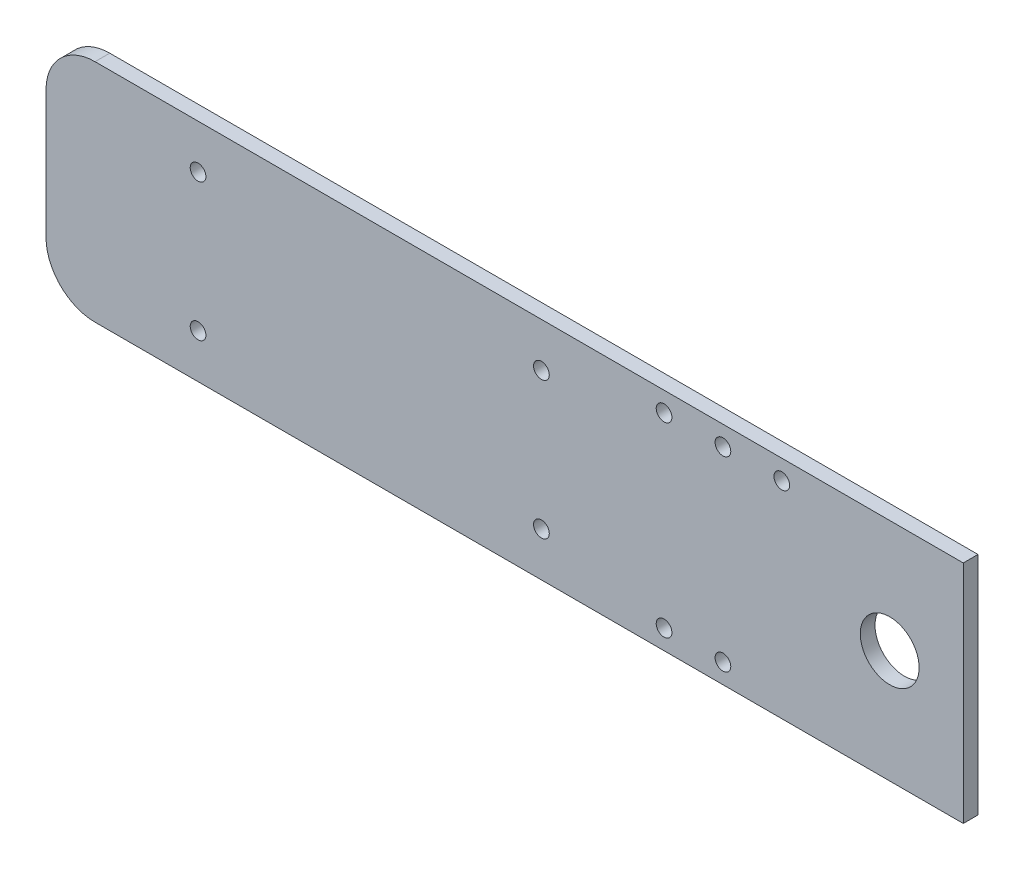
SolidWorks part; units mm, degrees
material "Acrylic (Medium-high impact)"
ref_plane "Front Plane" through (0, 0, 0) normal (0, 0, 1) x (1, 0, 0)
ref_plane "Top Plane" through (0, 0, 0) normal (0, 1, 0) x (1, 0, 0)
ref_plane "Right Plane" through (0, 0, 0) normal (1, 0, 0) x (0, 0, -1)
sketch "Sketch2" plane through (0, 0, 0) normal (0, 0, 1) x (1, 0, 0)
  line L0 (56, 23) -> (56, 17)
  line L1 (56, -23) -> (-56, -23)
  line L2 (56, -23) -> (56, 23)
  line L3 (56, 23) -> (-56, 23)
  line L4 (-56, -23) -> (-56, 23)
  line L5 (56, -23) -> (-56, 23) construction
  line L6 (56, 23) -> (-56, -23) construction
  line L7 (56, 23) -> (86, 23)
  line L8 (56, 23) -> (56, -23)
  line L9 (56, -23) -> (86, -23)
  line L10 (86, 23) -> (86, -23)
  line L11 (0, 0) -> (10, 0)
  line L12 (56, -23) -> (56, -17)
  line L13 (10, 0) -> (10, -14)
  line L14 (10, -14) -> (45, -14)
  circle A0 centre (45, -14) radius 1.6
  circle A1 centre (-25, -14) radius 1.6
  circle A2 centre (45, 14) radius 1.6
  circle A3 centre (-25, 14) radius 1.6
  point P0 (0, 0)
  dimension "D7" = 3.2
  dimension "D1" = 112
  dimension "D2" = 46
  dimension "D3" = 30
  dimension "D4" = 10
  dimension "D5" = 35
  dimension "D6" = 14
extrude "Boss-Extrude1" add sketch "Sketch2" along normal blind 3 contours L4 L1 L2 L3 | L8 L10 region at (71, 0, 0) region at (-0.0628, 0, 0)
sketch "Sketch3" plane through (0, 0, 3) normal (0, 0, 1) x (1, 0, 0)
  line L0 (86, 23) -> (86, -23)
  line L1 (86, 23) -> (66, 23)
  line L2 (86, -23) -> (66, -23)
  line L3 (66, 23) -> (66, -23)
  line L4 (-56, 23) -> (-56, -23)
  line L5 (-56, -23) -> (86, -23)
  line L6 (86, -23) -> (86, 23)
  line L7 (-56, -23) -> (86, -23)
  line L8 (-56, 23) -> (-56, -23)
  line L10 (86, -23) -> (86, 23)
  line L12 (86, 23) -> (66, 23)
  line L13 (86, 19) -> (66, 19)
  line L14 (66, -19) -> (86, -19)
  line L15 (70, 23) -> (70, -19)
  line L16 (86, 0) -> (116, 0)
  line L17 (82, 23) -> (82, -23)
  line L18 (66, 0) -> (-44, 0)
  line L19 (-44, 0) -> (-44, 19)
  line L20 (-44, 19) -> (56, 19)
  line L21 (86, 14) -> (97, 14)
  line L22 (97, 14) -> (97, 23)
  line L23 (97, 23) -> (86, 23)
  line L24 (82, 19) -> (94, 19)
  line L25 (86, -14) -> (97, -14)
  line L26 (97, -23) -> (86, -23)
  line L27 (97, -14) -> (97, -23)
  line L28 (86, -19) -> (70, -19) construction
  line L29 (70, 23) -> (70, -19) construction
  line L31 (86, -23) -> (131, -23)
  line L32 (86, -23) -> (86, 23)
  line L33 (86, 23) -> (-56, 23)
  line L34 (86, 23) -> (-56, 23)
  line L35 (86, 23) -> (131, 23)
  line L36 (131, -23) -> (131, 23)
  circle A0 centre (70, 19) radius 1.6
  circle A1 centre (82, 19) radius 1.6
  circle A2 centre (82, -19) radius 1.6
  circle A3 centre (70, -19) radius 1.6
  circle A4 centre (-44, 19) radius 1.6
  circle A5 centre (56, 19) radius 1.6
  circle A6 centre (-44, -19) radius 1.6
  circle A7 centre (56, -19) radius 1.6
  circle A8 centre (86, 0) radius 14
  circle A9 centre (94, 19) radius 1.6
  circle A10 centre (94, -19) radius 1.6
  circle A11 centre (116, 0) radius 6
  point P25 (82, 19)
  point P26 (-44, 9.5)
  point P27 (70, -19)
  line M13 (86, -23) -> (86, 23)
  dimension "D7" = 3.2
  dimension "D8" = 3.2
  dimension "D9" = 3.2
  dimension "D10" = 3.2
  dimension "D14" = 3.2
  dimension "D15" = 3.2
  dimension "D16" = 28
  dimension "D19" = 3.2
  dimension "D21" = 12
  dimension "D2" = 20
  dimension "D3" = 4
  dimension "D4" = 4
  dimension "D11" = 19
  dimension "D12" = 110
  dimension "D13" = 100
  dimension "D17" = 15
  dimension "D18" = 12
  dimension "D20" = 30
  dimension "D22" = 45
  dimension "D1" = 0
  dimension "D5" = 4
  dimension "D6" = 4
fillet "Fillet4" radius 10 2 edges at (-56, -23, 1.5) (-56, 23, 1.5)
extrude "Boss-Extrude2" add sketch "Sketch3" against normal blind 3 contours L27 L25 L10 L26 A10 M13 | A11 A8 L25 L27 L31 L36 L35 L22 L21 | A9 L10 L21 L22 L23 | A9 | A10 | L16 A8 M13 | A8 L16 M13 region at (94, 20.5547, 3) region at (91.2789, 18.4558, 3) region at (114, 22.3565, 3) region at (91.9418, 5.9418, 3) region at (91.9418, -5.9418, 3) region at (91.2789, -18.4558, 3) region at (94, -19, 3)
extrude "Cut-Extrude1" cut sketch "Sketch3<7>" against normal blind 3 contours L15 A0 L13 | L13 A0 L15 | L15 A0 L13 | L13 A0 L15 | A9 | L17 A1 L24 | L24 A1 L17 | L17 A1 L13 | L13 A1 L17 | L14 A3 L15 | L15 A3 L14 | L14 A3 | L14 A2 L17 | L17 A2 L14 | L14 A2 L17 | L17 A2 L14 region at (94, 20.5547, 3) region at (82.6791, 18.3209, 3) region at (82.6791, 19.6791, 3) region at (81.3209, 19.6791, 3) region at (81.3209, 18.3209, 3) region at (70.6791, 19.6791, 3) region at (69.3209, 19.6791, 3) region at (69.3209, 18.3209, 3) region at (70.6791, 18.3209, 3) region at (82.6791, -18.3209, 3) region at (81.3209, -18.3209, 3) region at (82.6791, -19.6791, 3) region at (81.3209, -19.6791, 3) region at (70.6791, -18.3209, 3) region at (69.3209, -18.3209, 3) region at (70, -19.6791, 3)
sketch "Sketch3<7>" plane through (0, 0, 3) normal (0, 0, 1) x (1, 0, 0) same geometry as "Sketch3"
